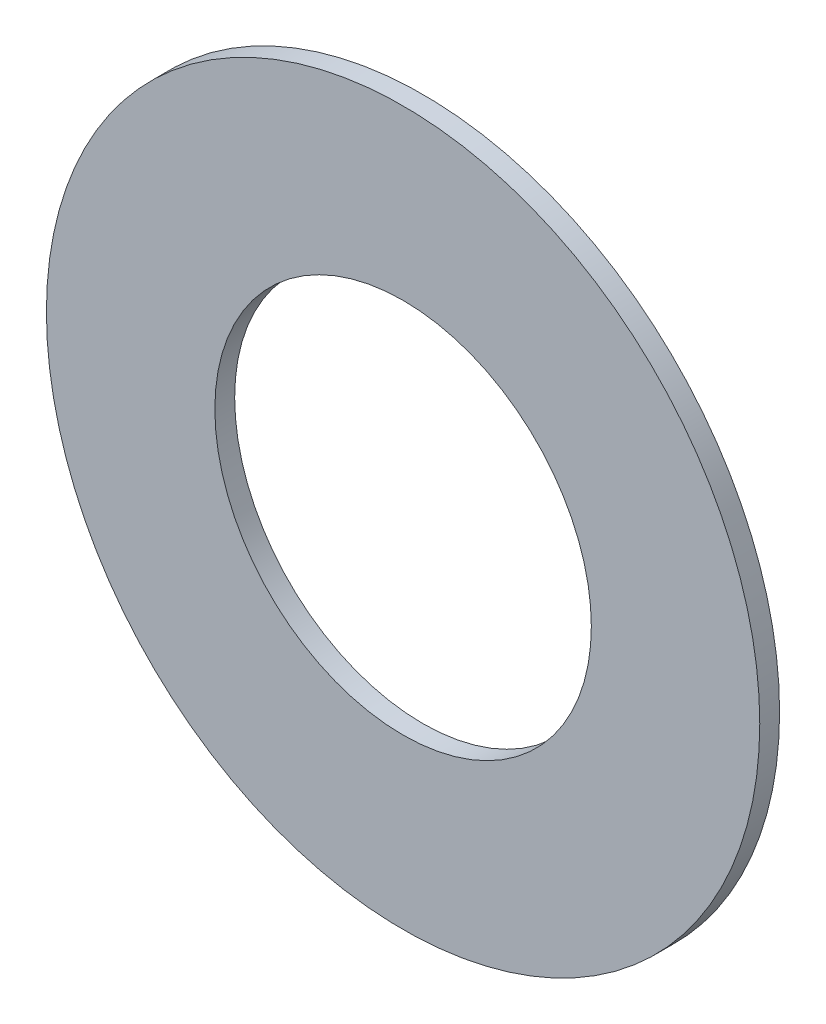
SolidWorks part; units mm, degrees
ref_plane "Спереди" through (0, 0, 0) normal (0, 0, 1) x (1, 0, 0)
ref_plane "Сверху" through (0, 0, 0) normal (0, 1, 0) x (1, 0, 0)
ref_plane "Справа" through (0, 0, 0) normal (1, 0, 0) x (0, 0, -1)
sketch "Эскиз1" plane through (0, 0, 0) normal (0, 0, 1) x (1, 0, 0)
  circle A0 centre (0, 0) radius 54
  circle A1 centre (0, 0) radius 28.5
  dimension "D1" = 108
  dimension "D2" = 57
extrude "Вытянуть1" add sketch "Эскиз1" along normal blind 3
ref_point "Точка1"
other "Точка маршрута1"
other "Точка соединения1" parameters "Диаметр"=100, "StubLength"=10
ref_axis "Ось1" through (0, 0, 13) along (0, 0, -1)
other "Точка соединения2" parameters "Диаметр"=50, "StubLength"=10
ref_axis "Ось2" through (0, 0, -10) along (0, 0, 1)
